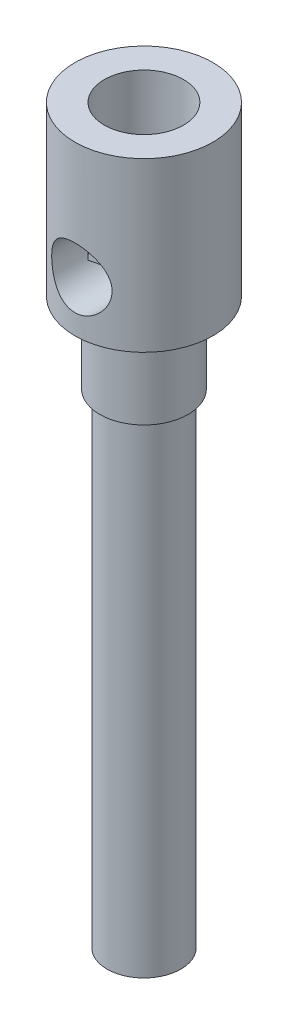
SolidWorks part; units mm, degrees
material "1023 Carbon Steel Sheet (SS)"
ref_plane "Front Plane" through (0, 0, 0) normal (0, 0, 1) x (1, 0, 0)
ref_plane "Top Plane" through (0, 0, 0) normal (0, 1, 0) x (1, 0, 0)
ref_plane "Right Plane" through (0, 0, 0) normal (1, 0, 0) x (0, 0, -1)
sketch "Sketch1" plane through (0, 0, 0) normal (0, 1, 0) x (1, 0, 0)
  circle A0 centre (0, 0) radius 2.58
  circle A1 centre (0, 0) radius 5.5
  circle A2 centre (0, 0) radius 4.58 construction
  dimension "D1" = 2
  dimension "D2" = 11
  dimension "D3" = 5.16
  dimension "D4" = 9.16
extrude "Boss-Extrude1" add sketch "Sketch1" along normal blind 72.14
sketch "Sketch2" plane through (0, 0, 0) normal (0, -1, 0) x (1, 0, 0)
  circle A0 centre (0, 0) radius 5.5
  circle A1 centre (0, 0) radius 5.5 construction
  circle A2 centre (0, 0) radius 5.5
  dimension "D1" = 11
sketch "Sketch4" plane through (0, 72.14, 0) normal (0, 1, 0) x (1, 0, 0)
  circle A0 centre (0, 0) radius 3.4
  circle A2 centre (0, 0) radius 5.5 construction
  dimension "D1" = 6.8
  dimension "D2" = 2.1
sketch "Sketch5" plane through (0, 72.14, 0) normal (0, 1, 0) x (1, 0, 0)
  circle A0 centre (0, 0) radius 6.5785
  circle M3 centre (0, 0) radius 5.5
  circle M4 centre (0, 0) radius 2.58
  dimension "D1" = 13.157
extrude "Boss-Extrude2" add sketch "Sketch5" along normal blind 12 contours M3 | A0 M3 | M4 region at (-6.3924, 72.14, 0) region at (-5.3444, 72.14, 0) region at (0, 72.14, 0)
sketch "Sketch6" plane through (0, 84.14, 0) normal (0, 1, 0) x (1, 0, 0)
  circle A0 centre (0, 0) radius 10.285
  circle M9 centre (0, 0) radius 6.5785
  dimension "D1" = 20.57
extrude "Boss-Extrude3" add sketch "Sketch6" along normal blind 25 contours A0 | M9 region at (-9.9941, 84.14, 0) region at (0, 84.14, 0)
hole_wizard "G1/4 Tapped Hole2" positions "Sketch10" profile "Sketch11" tap size "G1/4" standard "ISO"
sketch "Sketch10" plane through (0, 109.14, 0) normal (0, 1, 0) x (1, 0, 0)
  point P0 (0, 0)
sketch "Sketch11" plane through (0, 109.14, 0) normal (1, 0, 0) x (0, 0, 1)
  line L0 (0, 0) -> (0, 23.5451)
  line L1 (0, 23.5451) -> (5.9, 20)
  line L2 (5.9, 20) -> (5.9, 0)
  line L5 (5.9, 0) -> (0, 0)
  line L10 (0, 23.5451) -> (-5.9, 20) construction
  line L11 (0, -6.35) -> (0, 107.95) construction
  dimension "Tap Drill Dia." = 11.8
  dimension "Tap Drill Depth" = 20
  dimension "Drill Angle" = 118
cosmetic thread "Hole Thread1" parameters "D1"=15, "D2"=13.157
ref_plane "Plane1" through (0, 90.14, 0) normal (0, -1, 0) x (-1, 0, 0)
sketch "Sketch15" plane through (0, 90.14, 0) normal (0, -1, 0) x (-1, 0, 0)
  circle A0 centre (0, 0) radius 2.5
  dimension "D1" = 5
extrude "Boss-Extrude4" add sketch "Sketch15" along normal up to surface (18 mm away) contours A0 region at (0, 90.14, 0) up to face at (0, 72.14, 2.58)
hole_wizard "M8 Tapped Hole1" positions "Sketch16" profile "Sketch17" tap size "M8" standard "ISO"
sketch "Sketch16" plane through (0, 90.14, 0) normal (0, 1, 0) x (1, 0, 0)
  point P0 (0, 0)
sketch "Sketch17" plane through (0, 90.14, 0) normal (1, 0, 0) x (0, 0, 1)
  line L0 (0, 0) -> (0, 81.1829)
  line L1 (0, 81.1829) -> (3.4, 79.14)
  line L2 (3.4, 79.14) -> (3.4, 0)
  line L5 (3.4, 0) -> (0, 0)
  line L10 (0, 81.1829) -> (-3.4, 79.14) construction
  line L11 (0, -6.35) -> (0, 107.95) construction
  dimension "Tap Drill Dia." = 6.8
  dimension "Tap Drill Depth" = 79.14
  dimension "Drill Angle" = 118
cosmetic thread "Hole Thread2" parameters "D1"=10, "D2"=8
sketch "Sketch18" plane through (0, 0, 0) normal (0, 0, 1) x (1, 0, 0)
  line L0 (0, 87.14) -> (0, 91.64) construction
  line L2 (5.9, 87.14) -> (-5.9, 87.14) construction
  circle A0 centre (0, 91.64) radius 4.5
  point P7 (0, 87.14)
  dimension "D2" = 9
extrude "Cut-Extrude1" cut sketch "Sketch18" along normal blind 20 contours A0
equation "\"D1@Sketch6\"=20.57"
